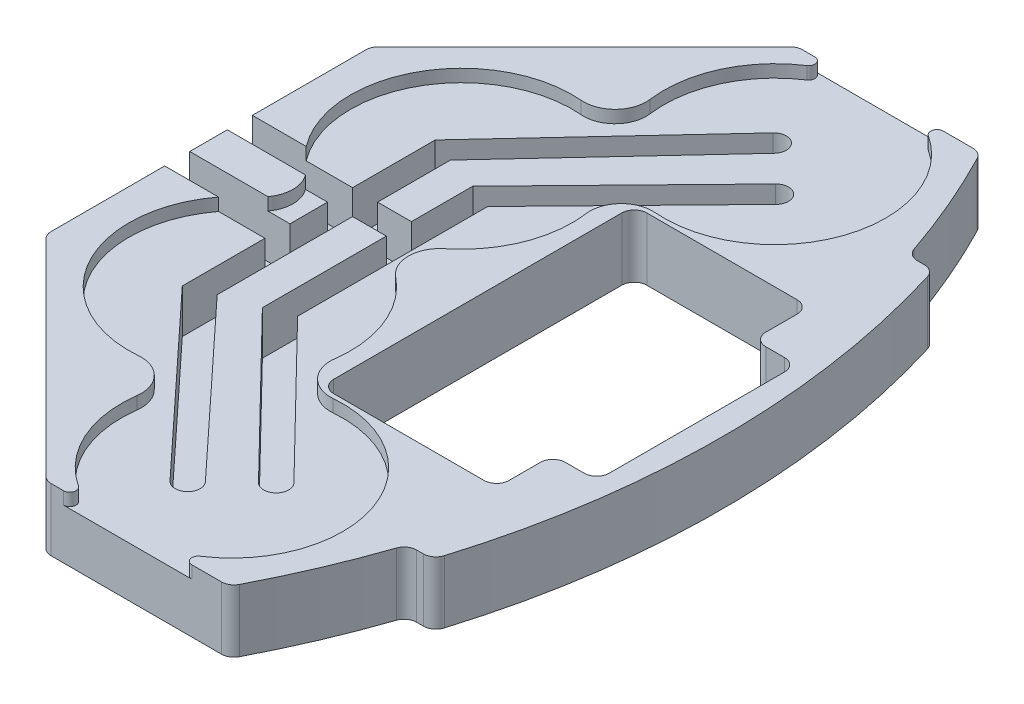
SolidWorks part; units mm, degrees
ref_plane "Front Plane" through (0, 0, 0) normal (0, 0, 1) x (1, 0, 0)
ref_plane "Top Plane" through (0, 0, 0) normal (0, 1, 0) x (1, 0, 0)
ref_plane "Right Plane" through (0, 0, 0) normal (1, 0, 0) x (0, 0, -1)
sketch "Sketch1" plane through (0, 0, 0) normal (0, 1, 0) x (1, 0, 0)
  line L0 (0, 0) -> (98.9949, 98.9949) construction
  line L1 (98.9949, -98.9949) -> (0, 0) construction
  line L2 (0, 0) -> (140, 0) construction
  line L3 (34.6482, 64.3467) -> (84.1457, 113.8442) construction
  line L4 (34.6482, 64.3467) -> (64.3467, 34.6482) construction
  line L5 (84.1457, 113.8442) -> (113.8442, 84.1457) construction
  line L6 (64.3467, 34.6482) -> (113.8442, 84.1457) construction
  line L7 (34.6482, 64.3467) -> (113.8442, 84.1457) construction
  line L8 (84.1457, 113.8442) -> (64.3467, 34.6482) construction
  line L9 (64.3467, -34.6482) -> (113.8442, -84.1457) construction
  line L10 (64.3467, -34.6482) -> (34.6482, -64.3467) construction
  line L11 (113.8442, -84.1457) -> (84.1457, -113.8442) construction
  line L12 (34.6482, -64.3467) -> (84.1457, -113.8442) construction
  line L13 (64.3467, -34.6482) -> (84.1457, -113.8442) construction
  line L14 (113.8442, -84.1457) -> (34.6482, -64.3467) construction
  line L15 (50, 25.9584) -> (84.0416, 60)
  line L16 (50, 25.9584) -> (50, 0)
  line L17 (50, 0) -> (132, 0)
  line L18 (95.4594, 65.7609) -> (91.2168, 61.5183) construction
  line L19 (95.4594, 65.7609) -> (80.6102, 80.6102) construction
  line L20 (84.0416, 60) -> (117.5755, 60)
  line L22 (91.2168, 61.5183) -> (76.3675, 76.3675) construction
  line L23 (80.6102, 80.6102) -> (76.3675, 76.3675) construction
  arc A0 (98.9949, 98.9949) -> (98.9949, -98.9949) centre (0, 0) cw construction
  arc A5 (117.5755, 60) -> (132, 0) centre (0, 0) cw
  point P6 (74.2462, 74.2462)
  point P7 (74.2462, -74.2462)
  dimension "D5" = 6
  dimension "D8" = 8
  dimension "D1" = 90
  dimension "D2" = 140
  dimension "D3" = 42
  dimension "D4" = 70
  dimension "D6" = 17
  dimension "D7" = 60
  dimension "D9" = 108
  dimension "D11" = 50
extrude "Boss-Extrude1" add sketch "Sketch1" along normal blind 10
sketch "Sketch2" plane through (0, 10, 0) normal (0, 1, 0) x (1, 0, 0)
  line L1 (55, 41.8225) -> (55, 0) construction
  line L2 (91, 0) -> (119, 0) construction
  line L3 (91, 0) -> (91, 25) construction
  line L4 (91, 25) -> (119, 25) construction
  line L5 (119, 0) -> (119, 25) construction
  line L6 (0, 0) -> (135.2492, 0) construction
  line L8 (84.0416, 60) -> (50, 25.9584) construction
  circle A0 centre (97.0961, 43.356) radius 17.705
  circle A1 centre (72.705, 17.7) radius 17.705
  arc A2 (112.5444, 54.9649) -> (125.2492, 0) centre (0, 0) cw construction
  line M10 (50, 0) -> (132, 0)
  dimension "D1" = 35.41
  dimension "D4" = 91
  dimension "D2" = 25
  dimension "D3" = 28
  dimension "D5" = 55
  dimension "D6" = 35.4
  dimension "D8" = 21
extrude "Cut-Extrude4" cut sketch "Sketch2" against normal blind 2 contours A1 A0 M10 | A1 A0 | A0 A1 region at (97.0962, 10, -43.3561) region at (84.9006, 10, -30.528) region at (72.7049, 10, -17.7)
mirror "Mirror2" about plane through (0, 0, 0) normal (0, 0, 1) of "Boss-Extrude1", "Cut-Extrude4"
fillet "Fillet3" radius 5 6 edges at (84.5956, 9, 30.8179) (85.2055, 9, 30.2381) (73.1257, 9, 0) (72.2843, 9, 0) (85.2055, 9, -30.2381) (84.5956, 9, -30.8179)
fillet "Fillet5" radius 1 4 edges at (103.1331, 9, 60) (91.0591, 9, 60) (103.1331, 9, -60) (91.0591, 9, -60)
sketch "Sketch3" plane through (0, 10, 0) normal (0, 1, 0) x (1, 0, 0)
  line L1 (93, 25) -> (121, 25)
  line L2 (93, 25) -> (93, -25)
  line L3 (93, -25) -> (121, -25)
  line L4 (121, 25) -> (121, -25)
  arc A1 (120.1047, 28.9976) -> (119.0668, -33.0014) centre (0, 0) cw construction
  dimension "D3" = 93
  dimension "D1" = 28
  dimension "D2" = 50
extrude "Cut-Extrude5" cut sketch "Sketch3" against normal up to next
sketch "Sketch6" plane through (0, 10, 0) normal (0, 1, 0) x (1, 0, 0)
  line L0 (121, -25) -> (121, 25) construction
  line L1 (121, 16) -> (128, 16)
  line L2 (121, 16) -> (121, -16)
  line L3 (121, -16) -> (128, -16)
  line L4 (128, 16) -> (128, -16)
  line L6 (93, 25) -> (93, -25) construction
  line L7 (93, 25) -> (93, -25) construction
  point P6 (93, 0)
  dimension "D1" = 32
  dimension "D2" = 16
  dimension "D3" = 35
extrude "Cut-Extrude8" cut sketch "Sketch6" against normal up to next
fillet "Fillet4" radius 2 8 edges at (121, 5, 25) (93, 5, 25) (121, 5, -25) (93, 5, -25) (121, 5, 16) (128, 5, 16) (121, 5, -16) (128, 5, -16)
sketch "Sketch4" plane through (0, 10, 0) normal (0, 1, 0) x (1, 0, 0)
  line L0 (97.0961, 43.356) -> (72.705, 17.7) construction
  line L1 (72.705, 17.7) -> (72.705, -17.7) construction
  line L2 (72.705, -17.7) -> (97.0961, -43.356) construction
  line L3 (93.4724, 46.8011) -> (100.7199, 39.911) construction
  line L4 (68.0065, 19.4101) -> (77.4035, 15.9899) construction
  line L5 (68.0065, -19.4101) -> (77.4035, -15.9899) construction
  line L6 (93.4724, -46.8011) -> (100.7199, -39.911) construction
  line L7 (93.4724, 46.8011) -> (68.0065, 19.4101) construction
  line L8 (68.0065, 19.4101) -> (68.0065, -19.4101) construction
  line L9 (68.0065, -19.4101) -> (93.4724, -46.8011) construction
  line L10 (100.7199, -39.911) -> (77.4035, -15.9899) construction
  line L11 (77.4035, -15.9899) -> (77.4035, 15.9899) construction
  line L12 (77.4035, 15.9899) -> (100.7199, 39.911) construction
  line L13 (92.0077, 48.1629) -> (66.0065, 20.1962)
  line L14 (66.0065, 20.1962) -> (66.0065, -20.1962)
  line L15 (66.0065, -20.1962) -> (92.0077, -48.1629)
  line L16 (94.9372, 45.4393) -> (70.0065, 18.624)
  line L17 (70.0065, 18.624) -> (70.0065, -18.624)
  line L18 (70.0065, -18.624) -> (94.9372, -45.4393)
  line L19 (102.1521, -38.515) -> (79.4035, -15.1764)
  line L20 (79.4035, -15.1764) -> (79.4035, 15.1764)
  line L21 (79.4035, 15.1764) -> (102.1521, 38.515)
  line L22 (99.2877, -41.307) -> (75.4035, -16.8034)
  line L23 (75.4035, -16.8034) -> (75.4035, 16.8034)
  line L24 (75.4035, 16.8034) -> (99.2877, 41.307)
  arc A1 (95.623, 25.7124) -> (106.8019, 58.1636) centre (97.0961, 43.356) ccw construction
  arc A2 (106.8019, -58.1636) -> (95.623, -25.7124) centre (97.0961, -43.356) ccw construction
  arc A4 (61.616, -3.8978) -> (74.1782, -35.3436) centre (72.705, -17.7) ccw construction
  arc A5 (74.1782, 35.3436) -> (61.616, 3.8978) centre (72.705, 17.7) ccw construction
  arc A12 (92.0077, 48.1629) -> (94.9372, 45.4393) centre (93.4724, 46.8011) cw
  arc A13 (92.0077, -48.1629) -> (94.9372, -45.4393) centre (93.4724, -46.8011) ccw
  arc A14 (102.1521, -38.515) -> (99.2877, -41.307) centre (100.7199, -39.911) cw
  arc A15 (102.1521, 38.515) -> (99.2877, 41.307) centre (100.7199, 39.911) ccw
  dimension "D2" = 2
  dimension "D1" = 10
  dimension "D3" = 70
  dimension "D4" = 70
  dimension "D5" = 2
  dimension "D7" = 2
extrude "Cut-Extrude6" cut sketch "Sketch4" against normal blind 9
sketch "Sketch5" plane through (0, 10, 0) normal (0, 1, 0) x (1, 0, 0)
  line L0 (50, 5) -> (75.4035, 5) construction
  line L1 (50, 25.9584) -> (50, -25.9584) construction
  line L2 (66.0065, -5) -> (50, -5) construction
  line L3 (66.0065, 20.1962) -> (66.0065, -20.1962) construction
  line L4 (75.4035, 16.8034) -> (75.4035, -16.8034) construction
  line L5 (50, 3) -> (75.4035, 3)
  line L6 (66.0065, -3) -> (50, -3)
  line L7 (50, 7) -> (75.4035, 7)
  line L8 (66.0065, -7) -> (50, -7)
  line L9 (50, 3) -> (50, 7)
  line L10 (75.4035, 3) -> (75.4035, 7)
  line L11 (66.0065, -3) -> (66.0065, -7)
  line L12 (50, -3) -> (50, -7)
  point P6 (50, 0)
  point P7 (50, 0)
  dimension "D1" = 5
  dimension "D2" = 5
  dimension "D3" = 2
  dimension "D4" = 2
extrude "Cut-Extrude7" cut sketch "Sketch5" against normal blind 9
sketch "Sketch8" plane through (0, 10, 0) normal (0, 1, 0) x (1, 0, 0)
  line L0 (117.5755, 60) -> (107.3501, 60) construction
  line L1 (117.5755, -60) -> (107.3501, -60) construction
  line L2 (121.7935, 40) -> (125.7935, 40)
  line L3 (121.7935, -40) -> (125.7935, -40)
  arc A0 (113.2857, 60) -> (121.7935, 40) centre (0, 0) cw
  arc A1 (125.7935, -40) -> (125.7935, 40) centre (0, 0) ccw
  arc A2 (117.5755, -60) -> (117.5755, 60) centre (0, 0) ccw construction
  arc A3 (113.2857, -60) -> (121.7935, -40) centre (0, 0) ccw
  dimension "D1" = 4
  dimension "D2" = 80
  dimension "D3" = 40
extrude "Cut-Extrude10" cut sketch "Sketch8" against normal through all and the other way through all flip side to cut
fillet "Fillet6" radius 2 10 edges at (84.0416, 5, 60) (50, 5, 25.9584) (50, 5, -25.9584) (84.0416, 5, -60) (113.2857, 5, -60) (121.7935, 5, -40) (125.7935, 5, -40) (121.7935, 5, 40) (125.7935, 5, 40) (113.2857, 5, 60)
